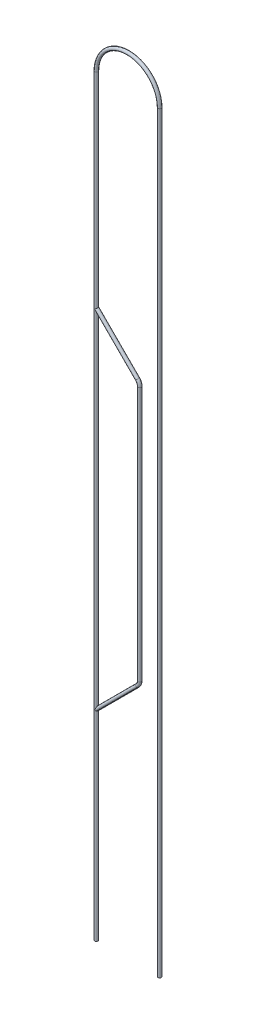
SolidWorks part; units mm, degrees
ref_plane "Plano frontal" through (0, 0, 0) normal (0, 0, 1) x (1, 0, 0)
ref_plane "Plano superior" through (0, 0, 0) normal (0, 1, 0) x (1, 0, 0)
ref_plane "Plano direito" through (0, 0, 0) normal (1, 0, 0) x (0, 0, -1)
sketch3d "3DSketch1"
  line L0 (-21754.0611, -1725.8675, 40706.6002) -> (-21754.0611, 11702.4259, 40706.6002)
  line L1 (-21754.0611, 11702.4259, 40706.6002) -> (-22901.7587, 11702.4259, 40706.6002) construction
  line L3 (-21754.0611, -1725.8675, 40706.6002) -> (-22980.8709, -1725.8675, 40706.6002) construction
  line L4 (-22901.7587, -1731.6744, 40674.6002) -> (-22901.7587, -1731.6744, 40723.8114) construction
  line L5 (-22901.7587, -1725.8675, 40706.6002) -> (-22901.7587, -1731.6744, 40706.6002) construction
  line L6 (-22901.7587, -1725.8675, 40706.6002) -> (-22901.7587, 11702.4259, 40706.6002)
  line L8 (-22901.7587, -1725.8675, 40706.6002) -> (-22901.7587, -1955.7787, 40706.6002)
  line L9 (-21754.0611, -1725.8675, 40706.6002) -> (-21754.0611, -1955.7787, 40706.6002)
  line L10 (-22901.7587, -1955.7787, 40706.6002) -> (-21754.0611, -1955.7787, 40706.6002) construction
  arc A0 (-21722.8613, -1725.8675, 40699.4891) -> (-21785.261, -1725.8675, 40699.4891) centre (-21754.0611, -1725.8675, 40706.6002) ccw construction
  arc A2 (-22870.5588, -1731.6744, 40699.4891) -> (-22932.9586, -1731.6744, 40699.4891) centre (-22901.7587, -1731.6744, 40706.6002) ccw construction
  arc A3 (-21754.0611, 11702.4259, 40706.6002) -> (-22901.7587, 11702.4259, 40706.6002) centre (-22327.9099, 11702.4259, 40706.6002) cw
  point P5 (-21754.0611, -1693.8675, 40706.6002)
  point P7 (-22901.7587, -1725.8675, 40706.6002)
  point P21 (-22901.7587, -1699.6744, 40706.6002)
  point P25 (-22327.9099, 11702.4259, 41280.449)
sweep "Sweep-Thin2" add path "3DSketch1" circular profile diameter 60 parameters "D1"=3, "D3"=60
sketch3d "3DSketch2"
  line L0 (-22901.7587, -1955.7787, 40706.6002) -> (-22901.7587, 11269.2213, 40706.6002) construction
  line L1 (-22901.7587, 11702.4259, 40706.6002) -> (-22901.7587, -1955.7787, 40706.6002) construction
  line L2 (-22901.7587, 7196.1342, 40706.6002) -> (-22114.7746, 7196.1342, 40706.6002) construction
  line L3 (-22114.7746, 7196.1342, 40706.6002) -> (-22114.7746, 2459.9165, 40706.6002) construction
  line L4 (-22114.7746, 2459.9165, 40706.6002) -> (-22901.7587, 2459.9165, 40706.6002) construction
  line L5 (-22901.7587, 7983.1182, 40706.6002) -> (-22154.8752, 7236.2347, 40706.6002)
  line L6 (-22114.7746, 7139.4234, 40706.6002) -> (-22114.7746, 2516.6272, 40706.6002)
  line L7 (-22154.8752, 2419.8159, 40706.6002) -> (-22901.7587, 1672.9324, 40706.6002)
  line L8 (-22850.5611, -2671.9747, 40199.9002) -> (-22850.5611, 12328.0253, 40199.9002) construction
  line L10 (-22799.5611, -2671.9747, 40199.9002) -> (-22901.5611, -2671.9747, 40199.9002) construction
  line L11 (-22901.5611, 12328.0253, 40199.9002) -> (-22799.5611, 12328.0253, 40199.9002) construction
  line L12 (-22850.5611, 4828.0253, 39732.9002) -> (-22114.7746, 4828.0253, 39732.9002) construction
  line L13 (-22114.7746, 4828.0253, 39732.9002) -> (-22114.7746, 4828.0253, 40706.6002) construction
  arc A0 (-22154.8752, 2419.8159, 40706.6002) -> (-22114.7746, 2516.6272, 40706.6002) centre (-22251.6865, 2516.6272, 40706.6002) ccw
  arc A1 (-22114.7746, 7139.4234, 40706.6002) -> (-22154.8752, 7236.2347, 40706.6002) centre (-22251.6865, 7139.4234, 40706.6002) ccw
  point P15 (-22114.7746, 2459.9165, 40706.6002)
  point P17 (-22251.6865, 2516.6272, 40843.512)
  point P20 (-22114.7746, 7196.1342, 40706.6002)
  point P22 (-22251.6865, 7139.4234, 40843.512)
  dimension "D3" = 136.9118
  dimension "D1" = 45
  dimension "D2" = 45
sweep "Sweep-Thin3" add path "3DSketch2" circular profile diameter 60 parameters "D1"=3, "D3"=60
